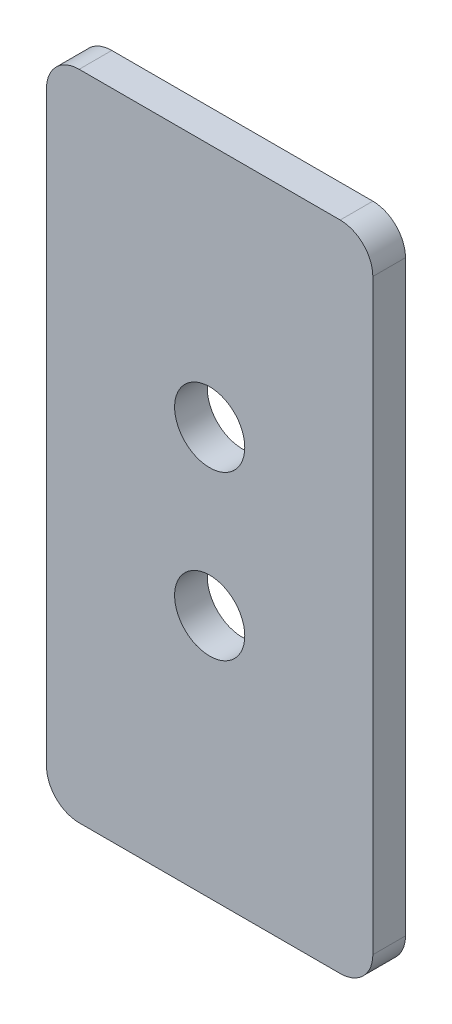
SolidWorks part; units mm, degrees
ref_plane "Front Plane" through (0, 0, 0) normal (0, 0, 1) x (1, 0, 0)
ref_plane "Top Plane" through (0, 0, 0) normal (0, 1, 0) x (1, 0, 0)
ref_plane "Right Plane" through (0, 0, 0) normal (1, 0, 0) x (0, 0, -1)
sketch "Sketch1" plane through (0, 0, 0) normal (0, 0, 1) x (1, 0, 0)
  line L0 (-10, -20) -> (-10, 20)
  line L1 (-10, -20) -> (10, -20)
  line L2 (-10, 20) -> (10, 20)
  line L3 (10, -20) -> (10, 20)
  line L4 (-10, -20) -> (10, 20) construction
  line L5 (-10, 20) -> (10, -20) construction
  line L6 (0, 5) -> (0, -5) construction
  circle A0 centre (0, -5) radius 2.15
  circle A1 centre (0, 5) radius 2.15
  point P1 (0, 0)
  point P22 (0, 0)
  dimension "D4" = 10
  dimension "D5" = 4.3
  dimension "D1" = 40
  dimension "D2" = 20
extrude "Boss-Extrude1" add sketch "Sketch1" along normal blind 2
chamfer "Chamfer1" [suppressed] distance 3 angle 15
chamfer "Chamfer2" [suppressed] distance 6 angle 35
sketch "Sketch2" plane through (0, 0, 2) normal (0, 0, 1) x (1, 0, 0)
  circle A0 centre (0, 5) radius 4
  circle A1 centre (0, -5) radius 4
  dimension "D1" = 8
extrude "Cut-Extrude1" [suppressed] cut sketch "Sketch2" against normal blind 6
fillet "Fillet1" radius 2 4 edges at (-10, 20, 1) (10, 20, 1) (-10, -20, 1) (10, -20, 1)
